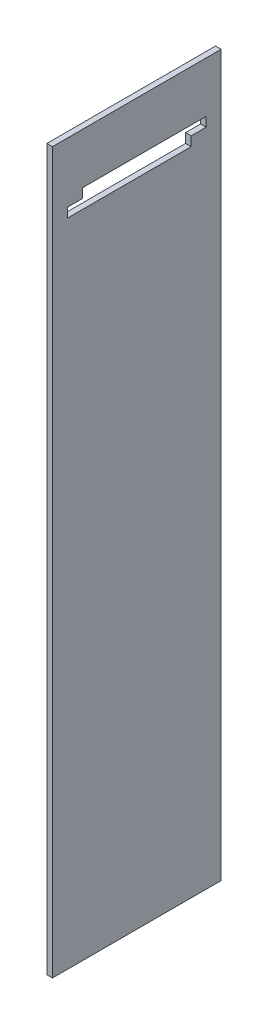
SolidWorks part; units mm, degrees
ref_plane "Front Plane" through (0, 0, 0) normal (0, 0, 1) x (1, 0, 0)
ref_plane "Top Plane" through (0, 0, 0) normal (0, 1, 0) x (1, 0, 0)
ref_plane "Right Plane" through (0, 0, 0) normal (1, 0, 0) x (0, 0, -1)
sketch "Sketch1" plane through (0, 0, 0) normal (0, 1, 0) x (1, 0, 0)
  line L1 (0, 0) -> (4.7625, 0)
  line L2 (0, 0) -> (0, 142.875)
  line L3 (0, 142.875) -> (4.7625, 142.875)
  line L4 (4.7625, 0) -> (4.7625, 142.875)
  dimension "D1" = 142.875
  dimension "D2" = 4.7625
extrude "Boss-Extrude1" add sketch "Sketch1" along normal blind 609.6
sketch "Sketch4" plane through (0, 0, 0) normal (-1, 0, 0) x (0, 0, 1)
  line L1 (-117.475, 550.8625) -> (-12.7, 550.8625)
  line L2 (-130.175, 558.8) -> (-130.175, 566.7375)
  line L3 (-130.175, 566.7375) -> (-25.4, 566.7375)
  line L4 (-12.7, 550.8625) -> (-12.7, 558.8)
  line L5 (0, 609.6) -> (0, 0) construction
  line L6 (-142.875, 609.6) -> (-142.875, 0) construction
  line L8 (-130.175, 558.8) -> (-117.475, 558.8)
  line L11 (-117.475, 558.8) -> (-117.475, 550.8625)
  line L14 (-12.7, 558.8) -> (-25.4, 558.8)
  line L15 (-25.4, 566.7375) -> (-25.4, 558.8)
  dimension "D1" = 12.7
  dimension "D2" = 12.7
  dimension "D3" = 12.7
  dimension "D4" = 12.7
extrude "Cut-Extrude2" cut sketch "Sketch4" against normal through all
